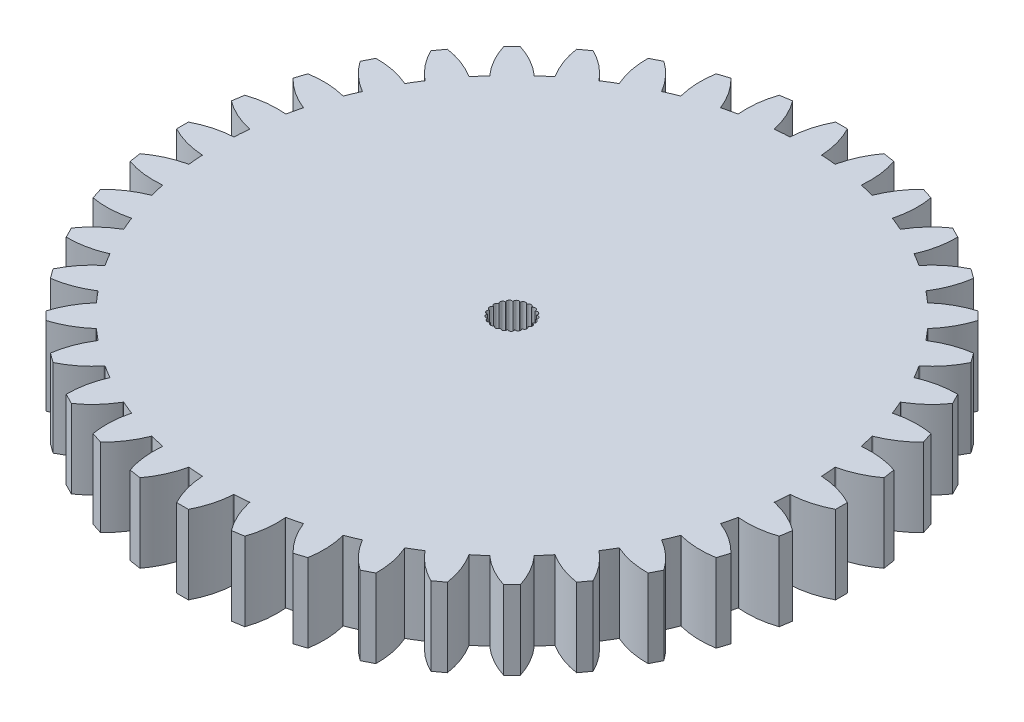
SolidWorks part; units mm, degrees
ref_plane "Front Plane" through (0, 0, 0) normal (0, 0, 1) x (1, 0, 0)
ref_plane "Top Plane" through (0, 0, 0) normal (0, 1, 0) x (1, 0, 0)
ref_plane "Right Plane" through (0, 0, 0) normal (1, 0, 0) x (0, 0, -1)
sketch "Sketch2" plane through (0, 0, 0) normal (0, 1, 0) x (1, 0, 0)
  line L0 (0, -10.2886) -> (0, 10.2886) construction
  line L1 (0, 0) -> (0.6267, 4.1579) construction
  line L2 (0, 0) -> (-0.6267, 4.1579) construction
  line L3 (0, 0) -> (0.687, 17.4865) construction
  line L4 (0, 0) -> (-0.687, 17.4865) construction
  line L5 (2, 37.5345) -> (1.9953, 37.4469)
  line L6 (-2, 37.5345) -> (-1.9953, 37.4469)
  line L7 (-0.75, 41.9933) -> (0.75, 41.9933)
  line L27 (34.3514, 15.2583) -> (34.2713, 15.2227)
  line L28 (32.5355, 18.8223) -> (32.4595, 18.7784)
  line L125 (-7.8471, 36.7595) -> (-7.8287, 36.6737) [skipped]
  line L126 (3.8963, 37.3852) -> (3.8872, 37.298) [skipped]
  line L127 (-3.8963, 37.3852) -> (-3.8872, 37.298) [skipped]
  line L128 (7.8471, 36.7595) -> (7.8287, 36.6737) [skipped]
  line L129 (-7.31, 41.359) -> (-5.8284, 41.5936) [skipped]
  line L130 (5.8284, 41.5936) -> (7.31, 41.359) [skipped]
  line L131 (-13.5009, 35.0794) -> (-13.4694, 34.9975) [skipped]
  line L132 (-9.6967, 36.3154) -> (-9.674, 36.2307) [skipped]
  line L133 (-13.6899, 39.7062) -> (-12.2634, 40.1698) [skipped]
  line L134 (-18.8223, 32.5355) -> (-18.7784, 32.4595) [skipped]
  line L135 (-15.2583, 34.3514) -> (-15.2227, 34.2713) [skipped]
  line L136 (-19.7328, 37.0758) -> (-18.3963, 37.7568) [skipped]
  line L137 (-23.6802, 29.1904) -> (-23.625, 29.1223) [skipped]
  line L138 (-20.4442, 31.5416) -> (-20.3965, 31.468) [skipped]
  line L139 (-25.2898, 33.5325) -> (-24.0763, 34.4141) [skipped]
  line L140 (-27.9551, 25.1267) -> (-27.8899, 25.068) [skipped]
  line L141 (-25.1267, 27.9551) -> (-25.068, 27.8899) [skipped]
  line L142 (-30.2241, 29.1634) -> (-29.1634, 30.2241) [skipped]
  line L143 (-31.5416, 20.4442) -> (-31.468, 20.3965) [skipped]
  line L144 (-29.1904, 23.6802) -> (-29.1223, 23.625) [skipped]
  line L145 (-34.4141, 24.0763) -> (-33.5325, 25.2898) [skipped]
  line L146 (-34.3514, 15.2583) -> (-34.2713, 15.2227) [skipped]
  line L147 (-32.5355, 18.8223) -> (-32.4595, 18.7784) [skipped]
  line L148 (-37.7568, 18.3963) -> (-37.0758, 19.7328) [skipped]
  line L149 (-36.3154, 9.6967) -> (-36.2307, 9.674) [skipped]
  line L150 (-35.0794, 13.5009) -> (-34.9975, 13.4694) [skipped]
  line L151 (-40.1698, 12.2634) -> (-39.7062, 13.6899) [skipped]
  line L152 (-37.3852, 3.8963) -> (-37.298, 3.8872) [skipped]
  line L153 (-36.7595, 7.8471) -> (-36.6737, 7.8287) [skipped]
  line L154 (-41.5936, 5.8284) -> (-41.359, 7.31) [skipped]
  line L155 (-37.5345, -2) -> (-37.4469, -1.9953) [skipped]
  line L156 (-37.5345, 2) -> (-37.4469, 1.9953) [skipped]
  line L157 (-41.9933, -0.75) -> (-41.9933, 0.75) [skipped]
  line L158 (-36.7595, -7.8471) -> (-36.6737, -7.8287) [skipped]
  line L159 (-37.3852, -3.8963) -> (-37.298, -3.8872) [skipped]
  line L160 (-41.359, -7.31) -> (-41.5936, -5.8284) [skipped]
  line L161 (-35.0794, -13.5009) -> (-34.9975, -13.4694) [skipped]
  line L162 (-36.3154, -9.6967) -> (-36.2307, -9.674) [skipped]
  line L163 (-39.7062, -13.6899) -> (-40.1698, -12.2634) [skipped]
  line L164 (-32.5355, -18.8223) -> (-32.4595, -18.7784) [skipped]
  line L165 (-34.3514, -15.2583) -> (-34.2713, -15.2227) [skipped]
  line L166 (-37.0758, -19.7328) -> (-37.7568, -18.3963) [skipped]
  line L167 (-29.1904, -23.6802) -> (-29.1223, -23.625) [skipped]
  line L168 (-31.5416, -20.4442) -> (-31.468, -20.3965) [skipped]
  line L169 (-33.5325, -25.2898) -> (-34.4141, -24.0763) [skipped]
  line L170 (-25.1267, -27.9551) -> (-25.068, -27.8899) [skipped]
  line L171 (-27.9551, -25.1267) -> (-27.8899, -25.068) [skipped]
  line L172 (-29.1634, -30.2241) -> (-30.2241, -29.1634) [skipped]
  line L173 (-20.4442, -31.5416) -> (-20.3965, -31.468) [skipped]
  line L174 (-23.6802, -29.1904) -> (-23.625, -29.1223) [skipped]
  line L175 (-24.0763, -34.4141) -> (-25.2898, -33.5325) [skipped]
  line L176 (-15.2583, -34.3514) -> (-15.2227, -34.2713) [skipped]
  line L177 (-18.8223, -32.5355) -> (-18.7784, -32.4595) [skipped]
  line L178 (-18.3963, -37.7568) -> (-19.7328, -37.0758) [skipped]
  line L179 (-9.6967, -36.3154) -> (-9.674, -36.2307) [skipped]
  line L180 (-13.5009, -35.0794) -> (-13.4694, -34.9975) [skipped]
  line L181 (-12.2634, -40.1698) -> (-13.6899, -39.7062) [skipped]
  line L182 (-3.8963, -37.3852) -> (-3.8872, -37.298) [skipped]
  line L183 (-7.8471, -36.7595) -> (-7.8287, -36.6737) [skipped]
  line L184 (-5.8284, -41.5936) -> (-7.31, -41.359) [skipped]
  line L185 (2, -37.5345) -> (1.9953, -37.4469) [skipped]
  line L186 (-2, -37.5345) -> (-1.9953, -37.4469) [skipped]
  line L187 (0.75, -41.9933) -> (-0.75, -41.9933) [skipped]
  line L188 (7.8471, -36.7595) -> (7.8287, -36.6737) [skipped]
  line L189 (3.8963, -37.3852) -> (3.8872, -37.298) [skipped]
  line L190 (7.31, -41.359) -> (5.8284, -41.5936) [skipped]
  line L191 (13.5009, -35.0794) -> (13.4694, -34.9975) [skipped]
  line L192 (9.6967, -36.3154) -> (9.674, -36.2307) [skipped]
  line L193 (13.6899, -39.7062) -> (12.2634, -40.1698) [skipped]
  line L194 (18.8223, -32.5355) -> (18.7784, -32.4595) [skipped]
  line L195 (15.2583, -34.3514) -> (15.2227, -34.2713) [skipped]
  line L196 (19.7328, -37.0758) -> (18.3963, -37.7568) [skipped]
  line L197 (23.6802, -29.1904) -> (23.625, -29.1223) [skipped]
  line L198 (20.4442, -31.5416) -> (20.3965, -31.468) [skipped]
  line L199 (25.2898, -33.5325) -> (24.0763, -34.4141) [skipped]
  line L200 (27.9551, -25.1267) -> (27.8899, -25.068) [skipped]
  line L201 (25.1267, -27.9551) -> (25.068, -27.8899) [skipped]
  line L202 (30.2241, -29.1634) -> (29.1634, -30.2241) [skipped]
  line L203 (31.5416, -20.4442) -> (31.468, -20.3965) [skipped]
  line L204 (29.1904, -23.6802) -> (29.1223, -23.625) [skipped]
  line L205 (34.4141, -24.0763) -> (33.5325, -25.2898) [skipped]
  line L206 (34.3514, -15.2583) -> (34.2713, -15.2227) [skipped]
  line L207 (32.5355, -18.8223) -> (32.4595, -18.7784) [skipped]
  line L208 (37.7568, -18.3963) -> (37.0758, -19.7328) [skipped]
  line L209 (36.3154, -9.6967) -> (36.2307, -9.674) [skipped]
  line L210 (35.0794, -13.5009) -> (34.9975, -13.4694) [skipped]
  line L211 (40.1698, -12.2634) -> (39.7062, -13.6899) [skipped]
  line L212 (37.3852, -3.8963) -> (37.298, -3.8872) [skipped]
  line L213 (36.7595, -7.8471) -> (36.6737, -7.8287) [skipped]
  line L214 (41.5936, -5.8284) -> (41.359, -7.31) [skipped]
  line L215 (37.5345, 2) -> (37.4469, 1.9953) [skipped]
  line L216 (37.5345, -2) -> (37.4469, -1.9953) [skipped]
  line L217 (41.9933, 0.75) -> (41.9933, -0.75) [skipped]
  line L218 (36.7595, 7.8471) -> (36.6737, 7.8287) [skipped]
  line L219 (37.3852, 3.8963) -> (37.298, 3.8872) [skipped]
  line L220 (41.359, 7.31) -> (41.5936, 5.8284) [skipped]
  line L221 (35.0794, 13.5009) -> (34.9975, 13.4694) [skipped]
  line L222 (36.3154, 9.6967) -> (36.2307, 9.674) [skipped]
  line L223 (39.7062, 13.6899) -> (40.1698, 12.2634) [skipped]
  line L224 (37.0758, 19.7328) -> (37.7568, 18.3963) [skipped]
  line L225 (29.1904, 23.6802) -> (29.1223, 23.625) [skipped]
  line L226 (31.5416, 20.4442) -> (31.468, 20.3965) [skipped]
  line L227 (33.5325, 25.2898) -> (34.4141, 24.0763) [skipped]
  line L228 (25.1267, 27.9551) -> (25.068, 27.8899) [skipped]
  line L229 (27.9551, 25.1267) -> (27.8899, 25.068) [skipped]
  line L230 (29.1634, 30.2241) -> (30.2241, 29.1634) [skipped]
  line L231 (20.4442, 31.5416) -> (20.3965, 31.468) [skipped]
  line L232 (23.6802, 29.1904) -> (23.625, 29.1223) [skipped]
  line L233 (24.0763, 34.4141) -> (25.2898, 33.5325) [skipped]
  line L234 (15.2583, 34.3514) -> (15.2227, 34.2713) [skipped]
  line L235 (18.8223, 32.5355) -> (18.7784, 32.4595) [skipped]
  line L236 (18.3963, 37.7568) -> (19.7328, 37.0758) [skipped]
  line L237 (9.6967, 36.3154) -> (9.674, 36.2307) [skipped]
  line L238 (13.5009, 35.0794) -> (13.4694, 34.9975) [skipped]
  line L239 (12.2634, 40.1698) -> (13.6899, 39.7062) [skipped]
  circle A0 centre (0, 0) radius 37.5877 construction
  circle A1 centre (0, 0) radius 2.2
  circle A2 centre (0, 0) radius 2.45 construction
  arc A3 (-0.3279, 2.1754) -> (0.3279, 2.1754) centre (0, 2.1169) cw
  arc A4 (0.3279, 2.1754) -> (0.9545, 1.9821) centre (0.624, 2.0229) cw
  arc A5 (0.9545, 1.9821) -> (1.4964, 1.6127) centre (1.1925, 1.7491) cw
  arc A6 (1.4964, 1.6127) -> (1.9053, 1.1) centre (1.6551, 1.3199) cw
  arc A7 (1.9053, 1.1) -> (2.1448, 0.4895) centre (1.9706, 0.7734) cw
  arc A8 (2.1448, 0.4895) -> (2.1938, -0.1644) centre (2.111, 0.1582) cw
  arc A9 (2.1938, -0.1644) -> (2.0479, -0.8038) centre (2.0639, -0.4711) cw
  arc A10 (2.0479, -0.8038) -> (1.72, -1.3717) centre (1.8333, -1.0585) cw
  arc A11 (1.72, -1.3717) -> (1.2393, -1.8177) centre (1.4399, -1.5518) cw
  arc A12 (1.2393, -1.8177) -> (0.6485, -2.1023) centre (0.9185, -1.9073) cw
  arc A13 (0.6485, -2.1023) -> (0, -2.2) centre (0.3155, -2.0933) cw
  arc A14 (0, -2.2) -> (-0.6485, -2.1023) centre (-0.3155, -2.0933) cw
  arc A15 (-0.6485, -2.1023) -> (-1.2393, -1.8177) centre (-0.9185, -1.9073) cw
  arc A16 (-1.2393, -1.8177) -> (-1.72, -1.3717) centre (-1.4399, -1.5518) cw
  arc A17 (-1.72, -1.3717) -> (-2.0479, -0.8038) centre (-1.8333, -1.0585) cw
  arc A18 (-2.0479, -0.8038) -> (-2.1938, -0.1644) centre (-2.0639, -0.4711) cw
  arc A19 (-2.1938, -0.1644) -> (-2.1448, 0.4895) centre (-2.111, 0.1582) cw
  arc A20 (-2.1448, 0.4895) -> (-1.9053, 1.1) centre (-1.9706, 0.7734) cw
  arc A21 (-1.9053, 1.1) -> (-1.4964, 1.6127) centre (-1.6551, 1.3199) cw
  arc A22 (-1.4964, 1.6127) -> (-0.9545, 1.9821) centre (-1.1925, 1.7491) cw
  arc A23 (-0.9545, 1.9821) -> (-0.3279, 2.1754) centre (-0.624, 2.0229) cw
  circle A24 centre (0, 0) radius 37.5
  circle A25 centre (0, 0) radius 40 construction
  circle A26 centre (0, 0) radius 42 construction
  arc A27 (0.75, 41.9933) -> (2, 37.5345) centre (-9.0634, 36.8375) cw
  arc A28 (-0.75, 41.9933) -> (-2, 37.5345) centre (9.0634, 36.8375) ccw
  arc A107 (-5.8284, 41.5936) -> (-3.8963, 37.3852) centre (-14.7145, 34.9662) cw [skipped]
  arc A108 (7.31, 41.359) -> (7.8471, 36.7595) centre (-3.1892, 37.8019) cw [skipped]
  arc A109 (-7.31, 41.359) -> (-7.8471, 36.7595) centre (3.1892, 37.8019) ccw [skipped]
  arc A110 (5.8284, 41.5936) -> (3.8963, 37.3852) centre (14.7145, 34.9662) ccw [skipped]
  arc A111 (-12.2634, 40.1698) -> (-9.6967, 36.3154) centre (-20.0033, 32.2338) cw [skipped]
  arc A112 (-13.6899, 39.7062) -> (-13.5009, 35.0794) centre (-2.7636, 37.8354) ccw [skipped]
  arc A113 (-18.3963, 37.7568) -> (-15.2583, 34.3514) centre (-24.7995, 28.7078) cw [skipped]
  arc A114 (-19.7328, 37.0758) -> (-18.8223, 32.5355) centre (-8.6483, 36.9372) ccw [skipped]
  arc A115 (-24.0763, 34.4141) -> (-20.4442, 31.5416) centre (-28.9851, 24.4748) cw [skipped]
  arc A116 (-25.2898, 33.5325) -> (-23.6802, 29.1904) centre (-14.3201, 35.1296) ccw [skipped]
  arc A117 (-29.1634, 30.2241) -> (-25.1267, 27.9551) centre (-32.4569, 19.6393) cw [skipped]
  arc A118 (-30.2241, 29.1634) -> (-27.9551, 25.1267) centre (-19.6393, 32.4569) ccw [skipped]
  arc A119 (-33.5325, 25.2898) -> (-29.1904, 23.6802) centre (-35.1296, 14.3201) cw [skipped]
  arc A120 (-34.4141, 24.0763) -> (-31.5416, 20.4442) centre (-24.4748, 28.9851) ccw [skipped]
  arc A121 (-37.0758, 19.7328) -> (-32.5355, 18.8223) centre (-36.9372, 8.6483) cw [skipped]
  arc A122 (-37.7568, 18.3963) -> (-34.3514, 15.2583) centre (-28.7078, 24.7995) ccw [skipped]
  arc A123 (-39.7062, 13.6899) -> (-35.0794, 13.5009) centre (-37.8354, 2.7636) cw [skipped]
  arc A124 (-40.1698, 12.2634) -> (-36.3154, 9.6967) centre (-32.2338, 20.0033) ccw [skipped]
  arc A125 (-41.359, 7.31) -> (-36.7595, 7.8471) centre (-37.8019, -3.1892) cw [skipped]
  arc A126 (-41.5936, 5.8284) -> (-37.3852, 3.8963) centre (-34.9662, 14.7145) ccw [skipped]
  arc A127 (-41.9933, 0.75) -> (-37.5345, 2) centre (-36.8375, -9.0634) cw [skipped]
  arc A128 (-41.9933, -0.75) -> (-37.5345, -2) centre (-36.8375, 9.0634) ccw [skipped]
  arc A129 (-41.5936, -5.8284) -> (-37.3852, -3.8963) centre (-34.9662, -14.7145) cw [skipped]
  arc A130 (-41.359, -7.31) -> (-36.7595, -7.8471) centre (-37.8019, 3.1892) ccw [skipped]
  arc A131 (-40.1698, -12.2634) -> (-36.3154, -9.6967) centre (-32.2338, -20.0033) cw [skipped]
  arc A132 (-39.7062, -13.6899) -> (-35.0794, -13.5009) centre (-37.8354, -2.7636) ccw [skipped]
  arc A133 (-37.7568, -18.3963) -> (-34.3514, -15.2583) centre (-28.7078, -24.7995) cw [skipped]
  arc A134 (-37.0758, -19.7328) -> (-32.5355, -18.8223) centre (-36.9372, -8.6483) ccw [skipped]
  arc A135 (-34.4141, -24.0763) -> (-31.5416, -20.4442) centre (-24.4748, -28.9851) cw [skipped]
  arc A136 (-33.5325, -25.2898) -> (-29.1904, -23.6802) centre (-35.1296, -14.3201) ccw [skipped]
  arc A137 (-30.2241, -29.1634) -> (-27.9551, -25.1267) centre (-19.6393, -32.4569) cw [skipped]
  arc A138 (-29.1634, -30.2241) -> (-25.1267, -27.9551) centre (-32.4569, -19.6393) ccw [skipped]
  arc A139 (-25.2898, -33.5325) -> (-23.6802, -29.1904) centre (-14.3201, -35.1296) cw [skipped]
  arc A140 (-24.0763, -34.4141) -> (-20.4442, -31.5416) centre (-28.9851, -24.4748) ccw [skipped]
  arc A141 (-19.7328, -37.0758) -> (-18.8223, -32.5355) centre (-8.6483, -36.9372) cw [skipped]
  arc A142 (-18.3963, -37.7568) -> (-15.2583, -34.3514) centre (-24.7995, -28.7078) ccw [skipped]
  arc A143 (-13.6899, -39.7062) -> (-13.5009, -35.0794) centre (-2.7636, -37.8354) cw [skipped]
  arc A144 (-12.2634, -40.1698) -> (-9.6967, -36.3154) centre (-20.0033, -32.2338) ccw [skipped]
  arc A145 (-7.31, -41.359) -> (-7.8471, -36.7595) centre (3.1892, -37.8019) cw [skipped]
  arc A146 (-5.8284, -41.5936) -> (-3.8963, -37.3852) centre (-14.7145, -34.9662) ccw [skipped]
  arc A147 (-0.75, -41.9933) -> (-2, -37.5345) centre (9.0634, -36.8375) cw [skipped]
  arc A148 (0.75, -41.9933) -> (2, -37.5345) centre (-9.0634, -36.8375) ccw [skipped]
  arc A149 (5.8284, -41.5936) -> (3.8963, -37.3852) centre (14.7145, -34.9662) cw [skipped]
  arc A150 (7.31, -41.359) -> (7.8471, -36.7595) centre (-3.1892, -37.8019) ccw [skipped]
  arc A151 (12.2634, -40.1698) -> (9.6967, -36.3154) centre (20.0033, -32.2338) cw [skipped]
  arc A152 (13.6899, -39.7062) -> (13.5009, -35.0794) centre (2.7636, -37.8354) ccw [skipped]
  arc A153 (18.3963, -37.7568) -> (15.2583, -34.3514) centre (24.7995, -28.7078) cw [skipped]
  arc A154 (19.7328, -37.0758) -> (18.8223, -32.5355) centre (8.6483, -36.9372) ccw [skipped]
  arc A155 (24.0763, -34.4141) -> (20.4442, -31.5416) centre (28.9851, -24.4748) cw [skipped]
  arc A156 (25.2898, -33.5325) -> (23.6802, -29.1904) centre (14.3201, -35.1296) ccw [skipped]
  arc A157 (29.1634, -30.2241) -> (25.1267, -27.9551) centre (32.4569, -19.6393) cw [skipped]
  arc A158 (30.2241, -29.1634) -> (27.9551, -25.1267) centre (19.6393, -32.4569) ccw [skipped]
  arc A159 (33.5325, -25.2898) -> (29.1904, -23.6802) centre (35.1296, -14.3201) cw [skipped]
  arc A160 (34.4141, -24.0763) -> (31.5416, -20.4442) centre (24.4748, -28.9851) ccw [skipped]
  arc A161 (37.0758, -19.7328) -> (32.5355, -18.8223) centre (36.9372, -8.6483) cw [skipped]
  arc A162 (37.7568, -18.3963) -> (34.3514, -15.2583) centre (28.7078, -24.7995) ccw [skipped]
  arc A163 (39.7062, -13.6899) -> (35.0794, -13.5009) centre (37.8354, -2.7636) cw [skipped]
  arc A164 (40.1698, -12.2634) -> (36.3154, -9.6967) centre (32.2338, -20.0033) ccw [skipped]
  arc A165 (41.359, -7.31) -> (36.7595, -7.8471) centre (37.8019, 3.1892) cw [skipped]
  arc A166 (41.5936, -5.8284) -> (37.3852, -3.8963) centre (34.9662, -14.7145) ccw [skipped]
  arc A167 (41.9933, -0.75) -> (37.5345, -2) centre (36.8375, 9.0634) cw [skipped]
  arc A168 (41.9933, 0.75) -> (37.5345, 2) centre (36.8375, -9.0634) ccw [skipped]
  arc A169 (41.5936, 5.8284) -> (37.3852, 3.8963) centre (34.9662, 14.7145) cw [skipped]
  arc A170 (41.359, 7.31) -> (36.7595, 7.8471) centre (37.8019, -3.1892) ccw [skipped]
  arc A171 (40.1698, 12.2634) -> (36.3154, 9.6967) centre (32.2338, 20.0033) cw [skipped]
  arc A172 (39.7062, 13.6899) -> (35.0794, 13.5009) centre (37.8354, 2.7636) ccw [skipped]
  arc A173 (37.7568, 18.3963) -> (34.3514, 15.2583) centre (28.7078, 24.7995) cw [skipped]
  arc A174 (37.0758, 19.7328) -> (32.5355, 18.8223) centre (36.9372, 8.6483) ccw [skipped]
  arc A175 (34.4141, 24.0763) -> (31.5416, 20.4442) centre (24.4748, 28.9851) cw [skipped]
  arc A176 (33.5325, 25.2898) -> (29.1904, 23.6802) centre (35.1296, 14.3201) ccw [skipped]
  arc A177 (30.2241, 29.1634) -> (27.9551, 25.1267) centre (19.6393, 32.4569) cw [skipped]
  arc A178 (29.1634, 30.2241) -> (25.1267, 27.9551) centre (32.4569, 19.6393) ccw [skipped]
  arc A179 (25.2898, 33.5325) -> (23.6802, 29.1904) centre (14.3201, 35.1296) cw [skipped]
  arc A180 (24.0763, 34.4141) -> (20.4442, 31.5416) centre (28.9851, 24.4748) ccw [skipped]
  arc A181 (19.7328, 37.0758) -> (18.8223, 32.5355) centre (8.6483, 36.9372) cw [skipped]
  arc A182 (18.3963, 37.7568) -> (15.2583, 34.3514) centre (24.7995, 28.7078) ccw [skipped]
  arc A183 (13.6899, 39.7062) -> (13.5009, 35.0794) centre (2.7636, 37.8354) cw [skipped]
  arc A184 (12.2634, 40.1698) -> (9.6967, 36.3154) centre (20.0033, 32.2338) ccw [skipped]
  point P7 (0, 0)
  point P30 (1.5704, 39.9692)
  point P78 (0, 0)
  point P226 (0, 0)
  dimension "D1" = 4.4
  dimension "D3" = 4.9
  dimension "D5" = 75.1754
  dimension "D6" = 75
  dimension "D7" = 80
  dimension "D8" = 84
  dimension "D2" = 8.571
  dimension "D9" = 2.25
  dimension "D11" = 1.5
  dimension "D12" = 4
  dimension "D4" = 21
  dimension "D10" = 40
extrude "Boss-Extrude1" add sketch "Sketch2" along normal blind 10 contours A24 A22 A23 A3 A4 A5 A6 A7 A8 A9 A10 region at (2.859, 0, -36.327)
extrude "Boss-Extrude2" add sketch "Sketch2<4>" along normal blind 10 contours L7 A28 L6 A24 L5 A27 region at (0, 0, -39.4369)
sketch "Sketch2<4>" plane through (0, 0, 0) normal (0, 1, 0) x (1, 0, 0) same geometry as "Sketch2"
pattern_circular "CirPattern1" count 40 over 360 about axis through (0, 10, 0) along (0, 1, 0) of "Boss-Extrude2"
equation "\"Module\"= 2"
equation "\"Teeth\"= 40"
equation "\"Pitch Diameter\"= \"Module\" * \"Teeth\""
equation "\"Outer Diamter\"= \"Pitch Diameter\" + ( 2 * \"Module\" )"
equation "\"Root Diameter\"= \"Pitch Diameter\" - ( 2.5 * \"Module\" )"
equation "\"Base Diamter\"= \"Pitch Diameter\" * cos ( 20 )"
equation "\"D5@Sketch2\"=\"Base Diamter\""
equation "\"D6@Sketch2\"=\"Root Diameter\""
equation "\"D7@Sketch2\"=\"Pitch Diameter\""
equation "\"D8@Sketch2\"=\"Outer Diamter\""
equation "\"D9@Sketch2\"=90 / \"Teeth\""
